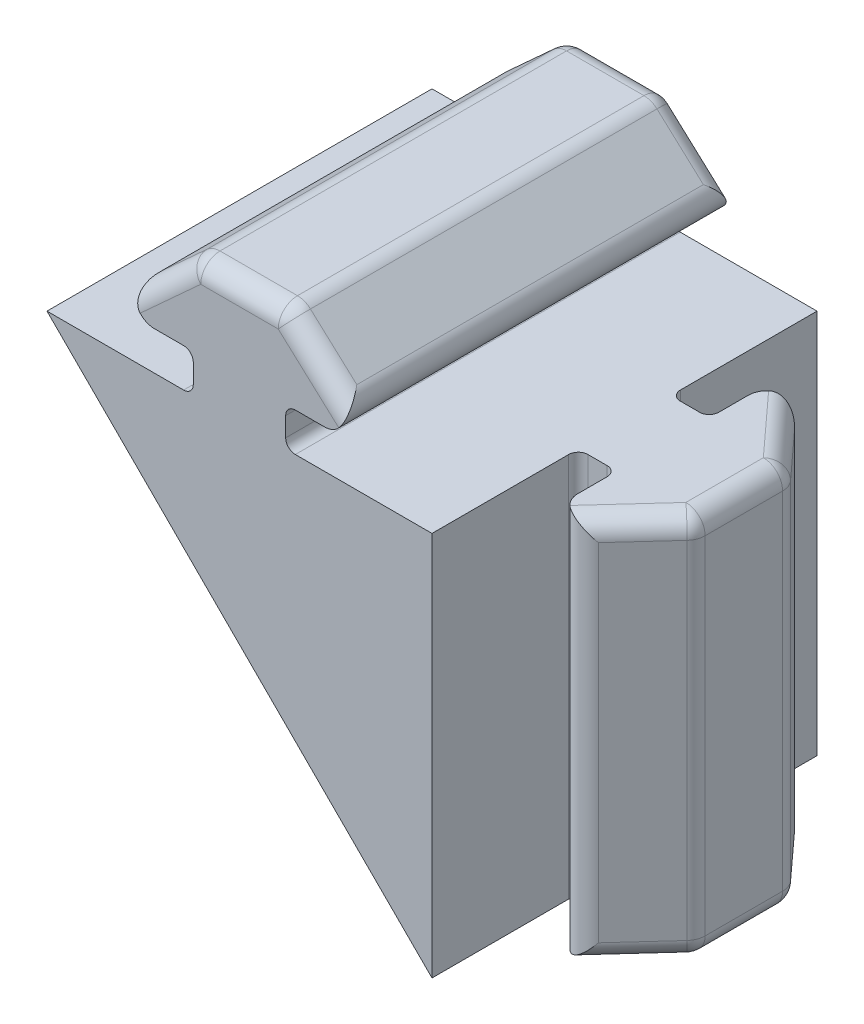
SolidWorks part; units mm, degrees
note: '?' marks a value the reader was unsure of.
ref_plane "Front Plane" through (0, 0, 0) normal (0, 0, 1) x (1, 0, 0)
ref_plane "Top Plane" through (0, 0, 0) normal (0, 1, 0) x (1, 0, 0)
ref_plane "Right Plane" through (0, 0, 0) normal (1, 0, 0) x (0, 0, -1)
sketch "Sketch1" plane through (0, 0, 0) normal (0, 0, 1) x (1, 0, 0)
  line L0 (10, 0) -> (10, 26.2) construction
  line L1 (7.6, 26.2) -> (12.4, 26.2)
  line L2 (12.4, 26.2) -> (17, 22)
  line L3 (17, 22) -> (12.4, 22)
  line L4 (12.4, 22) -> (12.4, 20)
  line L5 (12.4, 20) -> (20, 20)
  line L6 (20, 20) -> (20, 0)
  line L7 (20, 0) -> (0, 0)
  line L8 (0, 20) -> (0, 0)
  line L9 (7.6, 20) -> (0, 20)
  line L10 (7.6, 22) -> (7.6, 20)
  line L11 (3, 22) -> (7.6, 22)
  line L12 (7.6, 26.2) -> (3, 22)
  point P11 (10, 0)
  dimension "D1" = 2.4
  dimension "D2" = 6.2
  dimension "D3" = 7
  dimension "D4" = 2
  dimension "D5" = 10
  dimension "D6" = 4.8
  dimension "D7" = 20
sketch "Sketch2" plane through (0, 0, 0) normal (0, -1, 0) x (0, 0, -1)
  line L0 (10, 10) -> (10, 26.2) construction
  line L1 (7.6, 26.2) -> (12.4, 26.2)
  line L2 (12.4, 26.2) -> (17, 22)
  line L3 (17, 22) -> (12.4, 22)
  line L4 (12.4, 22) -> (12.4, 20)
  line L5 (12.4, 20) -> (20, 20)
  line L6 (20, 20) -> (20, 0)
  line L7 (20, 0) -> (0, 0)
  line L8 (0, 20) -> (0, 0)
  line L9 (7.6, 20) -> (0, 20)
  line L10 (7.6, 22) -> (7.6, 20)
  line L11 (3, 22) -> (7.6, 22)
  line L12 (7.6, 26.2) -> (3, 22)
  line L13 (20, 20) -> (0, 0) construction
  point P11 (10, 0)
  dimension "D1" = 2.4
  dimension "D2" = 6.2
  dimension "D3" = 7
  dimension "D4" = 2
  dimension "D5" = 10
  dimension "D6" = 4.8
  dimension "D7" = 20
  dimension "D8" = 10
extrude "Boss-Extrude1" add sketch "Sketch1" against normal blind 20
extrude "Boss-Extrude2" add sketch "Sketch2" against normal blind 20
ref_plane "Plane1" through (10, 10, 0) normal (0.7071, 0.7071, 0) x (0.7071, -0.7071, 0)
other "SurfaceCut1"
ref_axis "Axis1" [suppressed] through (0, 0, -20) along (0.5774, 0.5774, 0.5774)?
pattern_circular "CirPattern1" [suppressed] count 3 over 240 about axis through (0, 0, -20) along (0.5774, 0.5774, 0.5774)
mirror "Mirror1" [suppressed]
ref_plane "Plane2" [suppressed] through (13.3333, 13.3333, -13.3333) normal (-0.5774, -0.5774, 0.5774) x (-0.8165, 0.4082, -0.4082)
other "SurfaceCut2" [suppressed]
delete or keep bodies "Body-Delete/Keep 1" [suppressed] type delete bodies bodies 108
fillet "Fillet1" [suppressed] radius 1
fillet "Fillet2" [suppressed] radius 0.5
fillet "Fillet3" radius 1 20 edges at (3, 22, -10) (5.3, 24.1, -20) (5.3, 24.1, 0) (7.6, 26.2, -10) (10, 26.2, -20) (10, 26.2, 0) (12.4, 26.2, -10) (14.7, 24.1, -20) (17, 22, -10) (14.7, 24.1, 0) (24.1, 0, -14.7) (24.1, 20, -14.7) (22, 10, -17) (26.2, 0, -10) (26.2, 20, -10) (26.2, 10, -12.4) (22, 10, -3) (24.1, 0, -5.3) (24.1, 20, -5.3) (26.2, 10, -7.6)
fillet "Fillet4" radius 0.5 8 edges at (7.6, 22, -10) (7.6, 20, -10) (12.4, 22, -10) (12.4, 20, -10) (22, 10, -7.6) (22, 10, -12.4) (20, 10, -12.4) (20, 10, -7.6)
